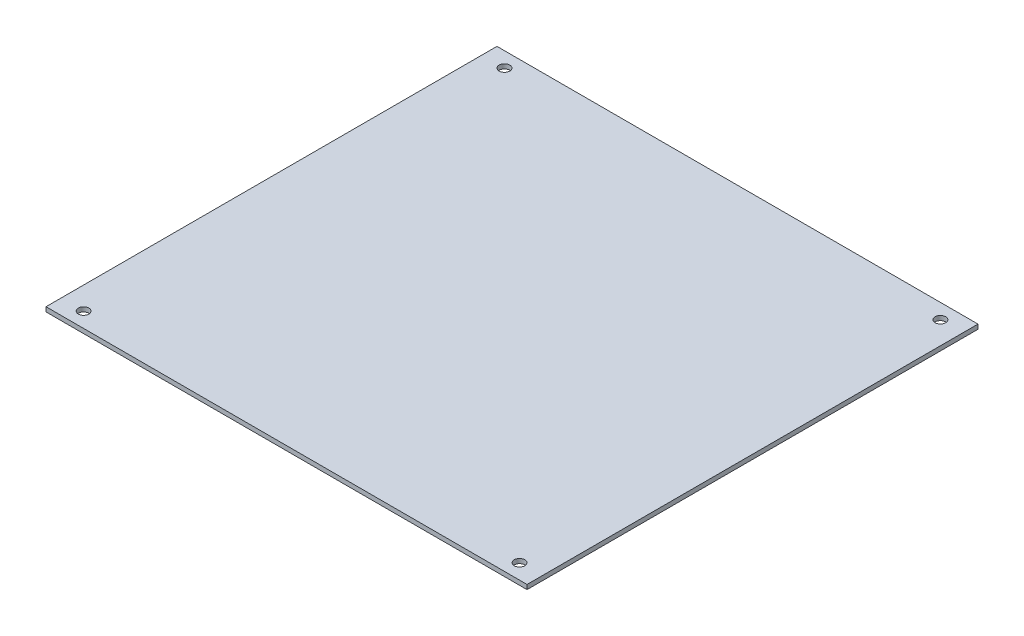
SolidWorks part; units mm, degrees
ref_plane "Alzado" through (0, 0, 0) normal (0, 0, 1) x (1, 0, 0)
ref_plane "Planta" through (0, 0, 0) normal (0, 1, 0) x (1, 0, 0)
ref_plane "Vista lateral" through (0, 0, 0) normal (1, 0, 0) x (0, 0, -1)
sketch "Croquis1" plane through (0, 0, 0) normal (0, 1, 0) x (1, 0, 0)
  line L0 (-80, 70) -> (-72.5, 70) construction
  line L1 (-80, 75) -> (80, 75)
  line L2 (-80, 75) -> (-80, -75)
  line L3 (-80, -75) -> (80, -75)
  line L4 (80, 75) -> (80, -75)
  line L5 (-80, 75) -> (80, -75) construction
  line L6 (-80, -75) -> (80, 75) construction
  line L7 (-72.5, 70) -> (72.5, 70) construction
  line L8 (72.5, 70) -> (80, 70) construction
  line L9 (0, 70) -> (0, 0) construction
  line L10 (0, 0) -> (-32.002, 0) construction
  circle A0 centre (-72.5, 70) radius 1.75
  circle A1 centre (72.5, 70) radius 1.75
  circle A2 centre (72.5, -70) radius 1.75
  circle A3 centre (-72.5, -70) radius 1.75
  point P0 (0, 0)
  dimension "D5" = 3.5
  dimension "D1" = 160
  dimension "D2" = 150
  dimension "D3" = 7.5
  dimension "D4" = 5
extrude "Saliente-Extruir1" add sketch "Croquis1" along normal blind 1.5
